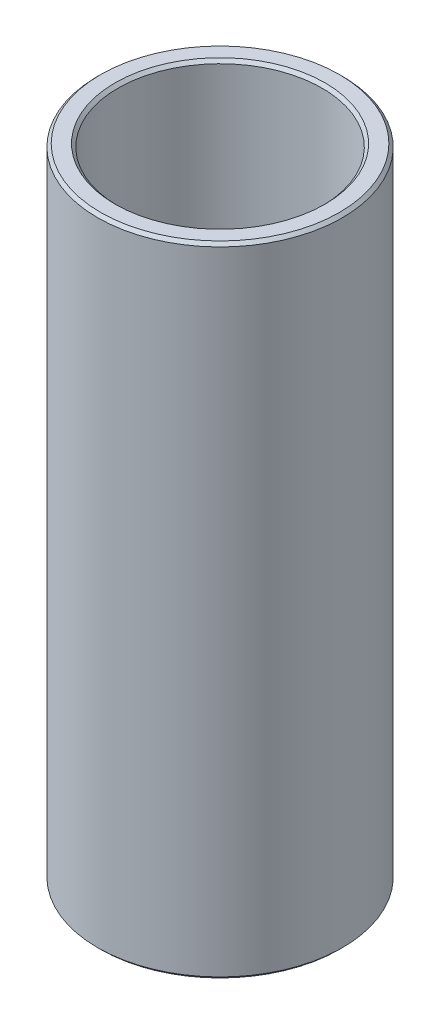
SolidWorks part; units mm, degrees
ref_plane "Front Plane" through (0, 0, 0) normal (0, 0, 1) x (1, 0, 0)
ref_plane "Top Plane" through (0, 0, 0) normal (0, 1, 0) x (1, 0, 0)
ref_plane "Right Plane" through (0, 0, 0) normal (1, 0, 0) x (0, 0, -1)
sketch "Sketch1" plane through (0, 0, 0) normal (0, 1, 0) x (1, 0, 0)
  circle A0 centre (0, 0) radius 40
  dimension "SLEEVE_OD" = 80
extrude "Boss-Extrude1" add sketch "Sketch1" along normal blind 208.5046
sketch "Sketch2" plane through (0, 0, 0) normal (0, 1, 0) x (1, 0, 0)
  circle A0 centre (0, 0) radius 33.3314
  dimension "BORE_D" = 66.6629
extrude "Cut-Extrude1" cut sketch "Sketch2" along normal through all
chamfer "Chamfer1" distance 0.9926 angle 45 4 edges at (0, 208.5046, 33.3314) (0, 0, 33.3314) (0, 0, 40) (0, 208.5046, 40)
